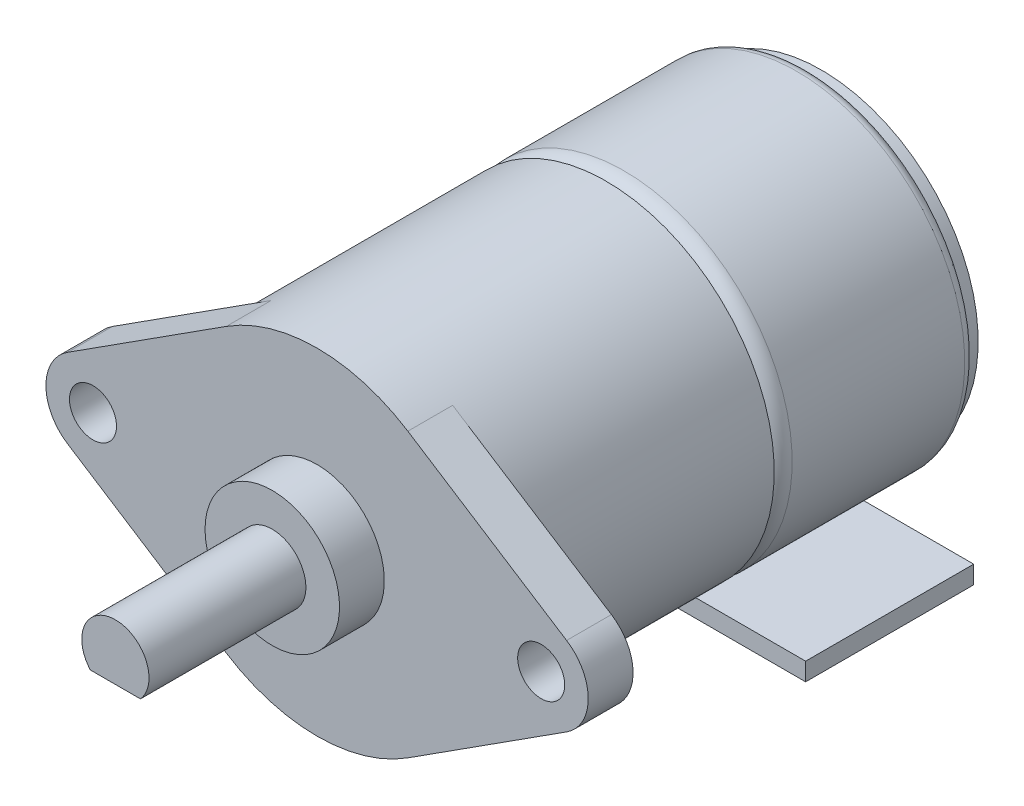
SolidWorks part; units mm, degrees
ref_plane "Front" through (0, 0, 0) normal (0, 0, 1) x (1, 0, 0)
ref_plane "Top" through (0, 0, 0) normal (0, 1, 0) x (1, 0, 0)
ref_plane "Right" through (0, 0, 0) normal (1, 0, 0) x (0, 0, -1)
sketch "Эскиз1" plane through (0, 0, 0) normal (0, 1, 0) x (1, 0, 0)
  line L0 (0, 0) -> (0, -39.2335) construction
  line L3 (-0.75, -0.5) -> (-3, -0.5)
  line L4 (-3, -0.5) -> (-3, -1.5)
  line L5 (-3, -1.5) -> (-7, -1.5)
  line L6 (-7, -1.5) -> (-7, -2.1)
  line L8 (-7.5, -2.6) -> (-7.5, -10.3)
  line L10 (-6.7, -11.1) -> (-6.7, -12) construction
  line L11 (-6.7, -12) -> (0, -12) construction
  line L12 (0, -12) -> (0, 0)
  line L14 (-7, -2.1) -> (-7, -2.6) construction
  line L15 (-6.7, -11.1) -> (-6.7, -10.3) construction
  line L16 (-6.7, -11.1) -> (-7.5, -11.1)
  line L17 (-7.5, -11.1) -> (-7.5, -24)
  line L18 (-7.5, -24) -> (-3, -24)
  line L19 (-3, -24) -> (-3, -26)
  line L20 (-3, -26) -> (-1.5, -26)
  line L21 (-1.5, -26) -> (-1.5, -33)
  line L22 (-1.5, -33) -> (0, -33)
  line L23 (0, -33) -> (0, -12)
  line L24 (-0.75, -0.5) -> (-0.75, -0.25)
  line L25 (-0.5, 0) -> (0, 0)
  arc A0 (-7, -2.1) -> (-7.5, -2.6) centre (-7, -2.6) ccw
  arc A1 (-7.5, -10.3) -> (-6.7, -11.1) centre (-6.7, -10.3) ccw
  arc A2 (-0.75, -0.25) -> (-0.5, 0) centre (-0.5, -0.25) cw
  dimension "D1" = 6
  dimension "D7" = 0.9
  dimension "D10" = 10.5
  dimension "D4" = 0.5
  dimension "D16" = 0.25
  dimension "D2" = 15
  dimension "D3" = 1
  dimension "D5" = 1.5
  dimension "D6" = 0.6
  dimension "D8" = 14
  dimension "D9" = 6.7
  dimension "D11" = 22.5
  dimension "D12" = 6
  dimension "D13" = 2
  dimension "D14" = 7
  dimension "D15" = 3
revolve "Motor" add sketch "Эскиз1" angle 360 about L0
sketch "Эскиз2" plane through (0, 0, 33) normal (0, 0, 1) x (1, 0, 0)
  line L0 (-1.118, -1) -> (1.118, -1)
  line L1 (-1.6853, 1.5) -> (1.9295, 1.5) construction
  arc A0 (1.118, -1) -> (-1.118, -1) centre (0, 0) ccw
  circle A1 centre (0, 0) radius 1.5 construction
  dimension "D1" = 2.5
extrude "Шпон-паз" cut sketch "Эскиз2" against normal blind 6.5 thin thin type one direction wall 1
sketch "Эскиз3" plane through (0, 0, 24) normal (0, 0, 1) x (1, 0, 0)
  line L0 (4.05, 6.3125) -> (11.134, 1.7675)
  line L1 (11.134, -1.7675) -> (4.05, -6.3125)
  line L2 (-10, 0) -> (10, 0) construction
  line L3 (-4.05, -6.3125) -> (-11.134, -1.7675)
  line L4 (-4.05, 6.3125) -> (-11.134, 1.7675)
  circle A0 centre (0, 0) radius 7.5 construction
  arc A1 (11.134, 1.7675) -> (11.134, -1.7675) centre (10, 0) cw
  circle A2 centre (10, 0) radius 1.05
  arc A3 (4.05, -6.3125) -> (-4.05, -6.3125) centre (0, 0) cw
  circle A4 centre (-10, 0) radius 1.05
  arc A5 (-11.134, -1.7675) -> (-11.134, 1.7675) centre (-10, 0) cw
  arc A6 (4.05, 6.3125) -> (-4.05, 6.3125) centre (0, 0) ccw
  point P12 (0, 0)
  dimension "D1" = 2.1
  dimension "D2" = 2.1
  dimension "D3" = 20
extrude "Держатель" add sketch "Эскиз3" against normal blind 2
ref_plane "Плоскость1" through (0, -7.5, 0) normal (0, -1, 0) x (-1, 0, 0)
sketch "Эскиз4" plane through (0, -7.5, 0) normal (0, -1, 0) x (-1, 0, 0)
  line L0 (0, -2.6) -> (0, -10.3) construction
  line L1 (3.5, -10.2) -> (-8, -10.2)
  line L2 (3.5, -10.2) -> (3.5, -2.7)
  line L3 (3.5, -2.7) -> (-8, -2.7)
  line L4 (-8, -10.2) -> (-8, -2.7)
  line L5 (3.5, -6.45) -> (-8, -6.45) construction
  line L7 (7.5, -10.3) -> (-7.5, -10.3) construction
  line L8 (7.5, -2.6) -> (-7.5, -2.6) construction
  point P5 (0, -6.45)
  dimension "D1" = 7.5
  dimension "D2" = 11.5
  dimension "D3" = 3.5
extrude "Плата" add sketch "Эскиз4" along normal blind 0.8 separate body
sketch "Пайка контактов" plane through (0, -8.3, 0) normal (0, -1, 0) x (1, 0, 0)
  line L0 (-0.75, 7.2) -> (2.25, 7.2) construction
  line L1 (0.75, 5.7) -> (-2.25, 5.7) construction
  line L2 (-0.75, 5.7) -> (-0.75, 7.2) construction
  line L3 (0, 2.6) -> (0, 10.3) construction
  line L5 (-0.75, 7.2) -> (0.75, 5.7) construction
  line L6 (-7.5, 10.3) -> (7.5, 10.3) construction
  line L7 (-7.5, 2.6) -> (7.5, 2.6) construction
  line L8 (7, 5.5333) -> (7, 3.7) construction
  line L9 (7, 7.3667) -> (7, 5.5333) construction
  line L10 (7, 7.3667) -> (7, 9.2) construction
  line L11 (7, 6.45) -> (8, 6.45) construction
  line L12 (8, 2.7) -> (8, 10.2) construction
  circle A0 centre (-2.25, 5.7) radius 0.75
  circle A1 centre (-0.75, 7.2) radius 0.75
  circle A2 centre (0.75, 5.7) radius 0.75
  circle A3 centre (2.25, 7.2) radius 0.75
  circle A4 centre (7, 3.7) radius 0.75
  circle A5 centre (7, 5.5333) radius 0.75
  circle A6 centre (7, 7.3667) radius 0.75
  circle A7 centre (7, 9.2) radius 0.75
  point P29 (8, 6.45)
  point P34 (0, 6.45)
  dimension "D1" = 1.5
  dimension "D4" = 1.5
  dimension "D2" = 3
  dimension "D3" = 1.5
  dimension "D5" = 5.5
  dimension "D6" = 1
extrude "Пайка" add sketch "Пайка контактов" along normal blind 0.7 draft 35
sketch "Эскиз6" plane through (0, -8.3, 0) normal (0, -1, 0) x (1, 0, 0)
  line L0 (5.7717, 10.2) -> (5.7717, 2.7) construction
  line L1 (8, 10.2) -> (-3.5, 10.2) construction
  line L2 (-3.5, 2.7) -> (8, 2.7) construction
  line L3 (-3.5, 8.1932) -> (8, 8.1932) construction
  line L4 (-3.5, 10.2) -> (-3.5, 2.7) construction
  line L5 (8, 2.7) -> (8, 10.2) construction
  text T0 "B1 B2 A1 A2" font "Century Gothic" height 0.85
  text T1 " B1 A2 B2 A1" font "Century Gothic" height 0.8
extrude "Надписи" add sketch "Эскиз6" along normal blind 0.01
